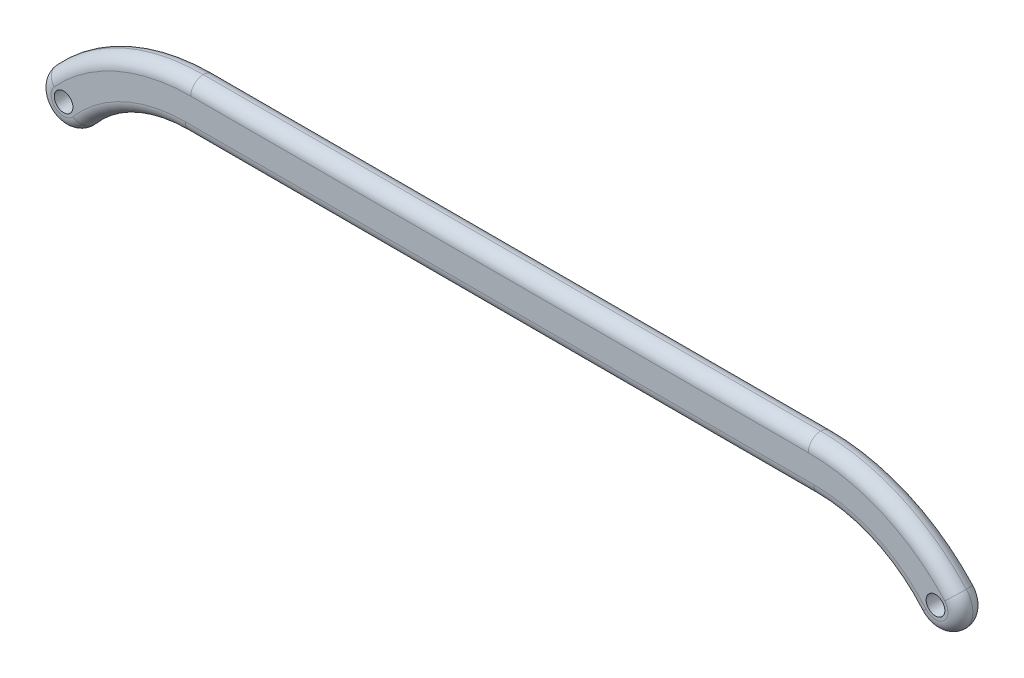
SolidWorks part; units mm, degrees
ref_plane "Front Plane" through (0, 0, 0) normal (0, 0, 1) x (1, 0, 0)
ref_plane "Top Plane" through (0, 0, 0) normal (0, 1, 0) x (1, 0, 0)
ref_plane "Right Plane" through (0, 0, 0) normal (1, 0, 0) x (0, 0, -1)
sketch "Sketch1" plane through (0, 0, 0) normal (0, 0, 1) x (1, 0, 0)
  line L0 (20.4301, 13) -> (119.5699, 13)
  line L1 (19.5292, 5) -> (120.4708, 5)
  line L3 (70, -25.359) -> (70, 47.9823) construction
  arc A0 (-2.9514, 2.6998) -> (3.0409, -2.5986) centre (0, 0) ccw
  arc A1 (-2.9514, 2.6998) -> (20.4301, 13) centre (20.4301, -18.6884) cw
  arc A2 (3.0409, -2.5986) -> (19.5292, 5) centre (19.5292, -16.6884) cw
  circle A3 centre (0, 0) radius 1.5
  circle A4 centre (140, 0) radius 1.5
  arc A5 (142.9514, 2.6998) -> (119.5699, 13) centre (119.5699, -18.6884) ccw
  arc A6 (142.9514, 2.6998) -> (136.9591, -2.5986) centre (140, 0) cw
  arc A7 (136.9591, -2.5986) -> (120.4708, 5) centre (120.4708, -16.6884) ccw
  point P11 (70, 13)
  point P21 (70, 5)
  dimension "D2" = 8
  dimension "D3" = 13
  dimension "D4" = 8
  dimension "10" = 3
  dimension "D1" = 70
extrude "Boss-Extrude1" add sketch "Sketch1" along normal blind 4
fillet "Fillet1" radius 2 16 edges at (10.4518, 3.009, 4) (-2.6496, -2.9966, 4) (7.6552, 10.3108, 4) (70, 13, 4) (132.3448, 10.3108, 4) (142.6496, -2.9966, 4) (129.5482, 3.009, 4) (10.4518, 3.009, 0) (-2.6496, -2.9966, 0) (7.6552, 10.3108, 0) (70, 13, 0) (132.3448, 10.3108, 0) (142.6496, -2.9966, 0) (129.5482, 3.009, 0) (70, 5, 4) (70, 5, 0)
